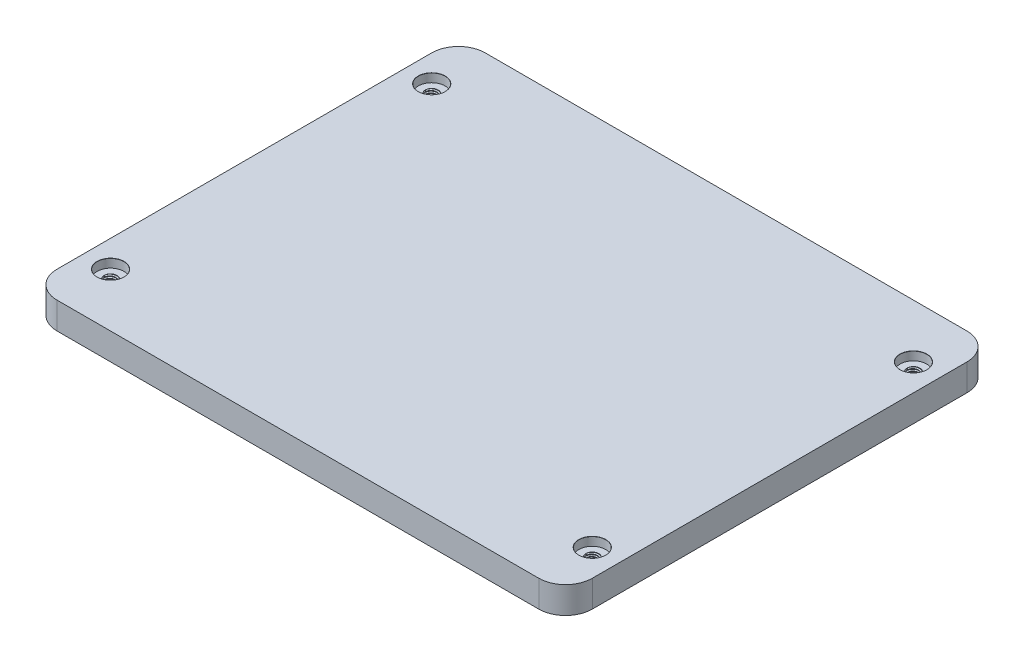
SolidWorks part; units mm, degrees
material "Polylactic Acid (PLA)"
ref_plane "Front Plane" through (0, 0, 0) normal (0, 0, 1) x (1, 0, 0)
ref_plane "Top Plane" through (0, 0, 0) normal (0, 1, 0) x (1, 0, 0)
ref_plane "Right Plane" through (0, 0, 0) normal (1, 0, 0) x (0, 0, -1)
sketch "Sketch1" plane through (0, 0, 0) normal (0, 1, 0) x (1, 0, 0)
  line L1 (-50, 40) -> (50, 40)
  line L2 (-50, 40) -> (-50, -40)
  line L3 (-50, -40) -> (50, -40)
  line L4 (50, 40) -> (50, -40)
extrude "Boss-Extrude1" add sketch "Sketch1" along normal blind 5
fillet "Fillet1" radius 5 4 edges at (-50, 2.5, 40) (-50, 2.5, -40) (50, 2.5, -40) (50, 2.5, 40)
sketch "Sketch4" plane through (0, 0, 0) normal (0, -1, 0) x (1, 0, 0)
  line L0 (50, 35) -> (40, 35) construction
  line L1 (45, 40) -> (45, 30) construction
  line L2 (45, 30) -> (40, 30) construction
  line L3 (24.1369, 29.0334) -> (25.2186, 29.3663)
  line L4 (40, 30) -> (40, 35) construction
  line L7 (20, 22.5) -> (40, 22.5) construction
  line L8 (23.9911, 24.9279) -> (23.9911, 25.2881)
  line L9 (20, 15) -> (20, 30) construction
  line L10 (16.6771, 32.2424) -> (65.1289, 32.2424) construction
  line L11 (23.4179, 28.3033) -> (23.5685, 27.8658)
  line L12 (23.8006, 27.664) -> (23.6379, 27.664)
  line L13 (23.6132, 27.7358) -> (23.6379, 27.664)
  line L14 (25.2186, 24.795) -> (25.2186, 25.166)
  line L15 (25.2186, 24.795) -> (25.6926, 24.5777)
  line L16 (25.6926, 24.5777) -> (25.6926, 24.3305)
  line L17 (25.6926, 24.3305) -> (24.1369, 24.3305)
  line L18 (24.1369, 24.3305) -> (24.1369, 24.5777)
  line L19 (24.1369, 24.5777) -> (24.6778, 24.7441)
  line L20 (24.6778, 24.7441) -> (24.6778, 25.2482)
  line L21 (24.6778, 28.7221) -> (24.1369, 29.0334)
  line L22 (25.7907, 27.4095) -> (25.8287, 27.4185)
  line L23 (26.8715, 27.664) -> (26.8715, 27.3265)
  line L24 (25.7907, 27.2758) -> (25.8287, 27.2595)
  line L25 (25.7907, 27.2758) -> (25.7907, 27.4095)
  line L26 (26.276, 26.9098) -> (26.276, 25.9631)
  line L27 (27.7806, 27.4095) -> (28.1923, 27.504)
  line L28 (28.8891, 27.664) -> (28.8891, 27.4814)
  line L29 (28.8891, 24.9279) -> (29.3631, 24.7441)
  line L30 (29.3631, 24.7441) -> (29.3631, 24.5777)
  line L31 (29.3631, 24.5777) -> (28.3348, 24.3416)
  line L32 (28.3348, 24.3416) -> (28.3348, 24.7679)
  line L33 (27.7806, 27.2758) -> (27.7806, 27.4095)
  line L34 (28.2206, 27.1421) -> (27.7806, 27.2758)
  line L35 (28.3348, 27.0667) -> (28.3348, 27.0272)
  line L36 (28.3348, 27.0667) -> (28.2206, 27.1421)
  line L37 (31.8159, 27.5597) -> (31.8159, 26.8495)
  line L38 (31.6365, 26.6106) -> (31.8159, 26.6106)
  line L39 (29.653, 25.3798) -> (29.653, 25.3136)
  line L40 (29.653, 25.3798) -> (29.8723, 25.3798)
  line L41 (32.7631, 28.4005) -> (33.2555, 28.4866)
  line L42 (33.2555, 28.4866) -> (33.2555, 27.664)
  line L43 (33.2555, 27.664) -> (34.388, 27.664)
  line L44 (23.8006, 28.753) -> (23.8607, 28.7221)
  line L45 (34.388, 27.664) -> (34.3549, 27.5597)
  line L46 (34.2649, 27.2758) -> (33.2555, 27.2758)
  line L47 (33.2555, 27.2758) -> (33.2555, 27.1421)
  line L48 (34.3223, 24.795) -> (34.3223, 24.6583)
  line L49 (32.1722, 27.4814) -> (32.1722, 27.2758)
  line L50 (32.1722, 27.2758) -> (32.6728, 27.2758)
  line L51 (32.6728, 27.2758) -> (32.6728, 26.7919)
  line L52 (35.102, 26.6106) -> (35.102, 26.4555)
  line L53 (35.102, 26.4555) -> (35.7179, 26.4555)
  line L54 (35.102, 26.2142) -> (35.7445, 26.2142)
  line L55 (37.1536, 26.2142) -> (37.1536, 26.3177)
  line L56 (35.9575, 26.2142) -> (36.7435, 26.2142)
  line L57 (35.102, 26.2142) -> (35.102, 25.909)
  line L58 (37.1536, 25.0961) -> (37.1536, 24.795)
  line L59 (38.4913, 26.989) -> (38.4913, 27.664)
  line L60 (38.4913, 27.664) -> (37.4409, 27.4095)
  line L61 (37.4409, 27.4095) -> (37.4409, 27.2758)
  line L62 (37.4409, 27.2758) -> (37.7609, 27.223)
  line L63 (37.7609, 27.223) -> (37.8963, 27.034)
  line L64 (37.8963, 27.034) -> (37.8963, 26.6828)
  line L65 (37.8963, 24.795) -> (37.7609, 24.6596)
  line L66 (37.7609, 24.6596) -> (37.4409, 24.582)
  line L67 (37.4409, 24.582) -> (37.4409, 24.3957)
  line L68 (37.4409, 24.3957) -> (39.0904, 24.3957)
  line L69 (39.0904, 24.3957) -> (39.0904, 24.582)
  line L70 (39.0904, 24.582) -> (38.6208, 24.6596)
  line L71 (38.6208, 24.6596) -> (38.4913, 24.7891)
  line L72 (38.4913, 26.7674) -> (38.4913, 26.5402)
  line L73 (39.9275, 27.5597) -> (39.9275, 26.8166)
  line L74 (39.9275, 26.8166) -> (39.8208, 26.8166)
  line L75 (39.8208, 26.8166) -> (39.7141, 26.8166)
  line L76 (22.0048, 27.2602) -> (21.8423, 26.5307)
  line L77 (21.9179, 26.505) -> (22.1161, 27.2073)
  line L78 (22.103, 26.0379) -> (22.7036, 25.7137)
  line L79 (22.6206, 25.574) -> (22.0162, 25.909)
  line L80 (23.2002, 25.7455) -> (23.3743, 26.3369)
  line L81 (23.052, 25.8181) -> (23.2002, 26.406)
  line L82 (23.181, 26.9798) -> (22.5733, 27.4814)
  line L83 (23.0812, 26.8446) -> (22.4979, 27.3265)
  line L84 (22.2908, 27.2013) -> (22.5114, 26.5687)
  line L85 (22.5733, 26.3912) -> (22.7868, 25.779)
  line L86 (23.0578, 26.7674) -> (22.6689, 26.62)
  line L87 (23.0762, 26.5687) -> (22.737, 26.4402)
  line L88 (22.5114, 26.5687) -> (22.0453, 26.4061)
  line L89 (22.5733, 26.3912) -> (22.1238, 26.2344)
  line L90 (22.5666, 27.664) -> (23.5685, 27.8658)
  line L91 (22.5811, 27.5368) -> (23.6132, 27.7358)
  line L92 (23.865, 25.4242) -> (23.3346, 25.4845)
  line L93 (23.3261, 25.3798) -> (23.865, 25.2881)
  line L94 (23.865, 25.4242) -> (24.6778, 25.3798)
  line L95 (23.9911, 25.2881) -> (24.6778, 25.2482)
  line L96 (25.2186, 25.3259) -> (25.427, 25.2833)
  line L97 (25.2186, 25.166) -> (25.4322, 25.134)
  line L98 (23.7275, 26.505) -> (24.6778, 25.9051)
  line L99 (23.6379, 26.4078) -> (24.6778, 25.7455)
  line L100 (25.2186, 25.574) -> (25.482, 25.4059)
  line L101 (25.2186, 25.4059) -> (25.4319, 25.3041)
  line L102 (23.7779, 26.7674) -> (24.6778, 26.8446)
  line L103 (23.7729, 26.6106) -> (24.6778, 26.7005)
  line L104 (23.6547, 26.9798) -> (24.6778, 27.5942)
  line L105 (23.7545, 26.8446) -> (24.6778, 27.3711)
  line L106 (23.8006, 27.9163) -> (24.6778, 28.0839)
  line L107 (23.8006, 27.7358) -> (24.6778, 27.9478)
  line L108 (25.2186, 28.188) -> (25.429, 28.245)
  line L109 (25.2186, 27.9972) -> (25.4286, 28.1334)
  line L110 (25.2186, 27.8658) -> (25.4604, 28.0298)
  line L111 (25.2186, 27.693) -> (25.5137, 27.9484)
  line L112 (25.8287, 27.8237) -> (25.8287, 27.4185)
  line L113 (25.9648, 27.8658) -> (25.9648, 27.4505)
  line L114 (25.2186, 26.9326) -> (25.8287, 27.01)
  line L115 (25.9648, 27.0272) -> (26.276, 27.0667)
  line L116 (25.8287, 27.2595) -> (25.8287, 27.01)
  line L117 (25.9648, 27.2008) -> (25.9648, 27.0272)
  line L118 (25.8287, 26.8495) -> (25.7907, 25.5752)
  line L119 (25.9648, 26.8679) -> (25.9207, 25.5513)
  line L120 (25.9648, 25.5312) -> (26.276, 25.9631)
  line L121 (26.056, 25.4614) -> (26.276, 25.7137)
  line L122 (26.0994, 25.4059) -> (26.276, 25.4614)
  line L123 (26.1361, 25.3306) -> (26.276, 25.3798)
  line L124 (26.0081, 27.8933) -> (26.3582, 27.5432)
  line L125 (26.0994, 27.991) -> (26.527, 27.5829)
  line L126 (27.0412, 26.7674) -> (26.8715, 26.5687)
  line L127 (26.9114, 26.9326) -> (26.8715, 26.8927)
  line L128 (26.8715, 27.3265) -> (26.9497, 27.2731)
  line L129 (26.8939, 27.1421) -> (26.8715, 27.1421)
  line L130 (27.4632, 26.7674) -> (27.711, 26.2685)
  line L131 (27.3697, 26.7198) -> (27.5783, 26.2142)
  line L132 (27.6163, 27.0272) -> (28.3348, 27.0272)
  line L133 (27.5783, 26.9) -> (28.3348, 26.9)
  line L134 (26.8939, 27.9647) -> (28.4733, 27.5686)
  line L135 (26.121, 28.0298) -> (28.1923, 27.504)
  line L136 (27.4144, 25.909) -> (26.8715, 25.7137)
  line L137 (27.4529, 25.7455) -> (26.8715, 25.5312)
  line L138 (28.143, 25.8562) -> (28.3348, 25.779)
  line L139 (28.0612, 25.6737) -> (28.3348, 25.6171)
  line L140 (28.1233, 26.0379) -> (28.3348, 26.1175)
  line L141 (28.143, 25.8562) -> (28.3348, 25.909)
  line L142 (26.1528, 28.1334) -> (31.9533, 28.0839)
  line L143 (31.8601, 27.9176) -> (26.8939, 27.9647)
  line L144 (28.8891, 27.4814) -> (29.8544, 27.1421)
  line L145 (28.8891, 27.2758) -> (29.7792, 27.0065)
  line L146 (28.8891, 27.0065) -> (29.7792, 27.0065)
  line L147 (28.8891, 26.8495) -> (29.7135, 26.8166)
  line L148 (28.8891, 26.296) -> (29.6945, 26.5298)
  line L149 (28.8891, 26.0923) -> (29.7213, 26.3818)
  line L150 (28.8891, 25.574) -> (29.653, 25.3136)
  line L151 (28.8891, 25.4059) -> (29.653, 25.134)
  line L152 (29.8846, 25.2482) -> (30.3505, 25.0581)
  line L153 (29.9427, 25.0581) -> (30.3234, 24.9197)
  line L154 (30.6896, 25.7137) -> (30.6896, 25.2859)
  line L155 (30.8482, 25.6638) -> (30.8482, 25.2498)
  line L156 (30.8831, 26.3177) -> (30.8831, 26.4109)
  line L157 (30.6896, 26.418) -> (30.6896, 26.3818)
  line L158 (30.9866, 25.134) -> (31.3847, 25.4213)
  line L159 (31.1642, 25.0961) -> (31.4723, 25.2859)
  line L160 (31.1642, 25.0961) -> (31.5169, 25.113)
  line L161 (31.0558, 24.9197) -> (31.4852, 24.9655)
  line L162 (30.5077, 26.989) -> (30.2376, 27.0667)
  line L163 (30.4364, 26.8166) -> (30.2071, 26.8166)
  line L164 (30.4364, 26.8166) -> (30.2138, 26.7674)
  line L165 (30.2758, 26.6106) -> (30.4484, 26.6623)
  line L166 (30.9866, 27.082) -> (31.1904, 27.2859)
  line L167 (31.0908, 26.989) -> (31.3189, 27.217)
  line L168 (31.1561, 26.8495) -> (31.6028, 26.8495)
  line L169 (31.1593, 26.7005) -> (31.6328, 26.7005)
  line L170 (31.5169, 27.6204) -> (31.8601, 27.9176)
  line L171 (31.7321, 27.5774) -> (32.0422, 27.8447)
  line L172 (32.5087, 27.7703) -> (32.5911, 27.6336)
  line L173 (32.6857, 28.0839) -> (32.7745, 28.0298)
  line L174 (31.8159, 26.8495) -> (32.6728, 26.7919)
  line L175 (31.8159, 26.6623) -> (32.6728, 26.6623)
  line L176 (31.9206, 25.7137) -> (32.6728, 26.1494)
  line L177 (31.9632, 25.5312) -> (32.6728, 25.9631)
  line L178 (31.9854, 25.209) -> (32.6728, 25.2498)
  line L179 (31.9693, 25.0206) -> (32.6728, 25.0961)
  line L180 (33.2555, 27.1421) -> (33.5099, 26.8755)
  line L181 (33.2555, 26.9768) -> (33.443, 26.7892)
  line L182 (33.2555, 26.7674) -> (33.4318, 26.7674)
  line L183 (33.2555, 26.6106) -> (33.3965, 26.6106)
  line L184 (33.2555, 26.4555) -> (33.3989, 26.5687)
  line L185 (33.2555, 26.296) -> (33.4515, 26.4176)
  line L186 (33.2555, 25.3136) -> (34.486, 25.4616)
  line L187 (33.2555, 25.134) -> (34.5302, 25.3139)
  line L188 (34.3549, 27.5597) -> (34.9324, 27.3384)
  line L189 (34.2951, 27.3711) -> (34.8203, 27.2046)
  line L190 (34.692, 27.0062) -> (34.0937, 26.7674)
  line L191 (34.5767, 26.7674) -> (34.1289, 26.6106)
  line L192 (34.4439, 26.1215) -> (34.0602, 26.397)
  line L193 (34.4649, 26.2977) -> (34.1134, 26.505)
  line L194 (35.4524, 26.9326) -> (35.2151, 26.9326)
  line L195 (35.5168, 27.188) -> (35.3905, 27.223)
  line L196 (35.7179, 26.4555) -> (35.688, 26.6336)
  line L197 (35.9062, 26.4555) -> (35.8504, 26.6122)
  line L198 (36.4355, 27.0667) -> (36.1709, 27.0667)
  line L199 (36.5053, 26.8726) -> (36.167, 26.8726)
  line L200 (37.1898, 27.034) -> (37.0286, 27.034)
  line L201 (37.1536, 26.3177) -> (37.2762, 26.4403)
  line L202 (35.6384, 25.3798) -> (35.1985, 25.3798)
  line L203 (35.688, 25.5639) -> (35.102, 25.909)
  line L204 (35.1462, 25.5312) -> (35.4524, 25.5312)
  line L205 (35.4524, 25.5312) -> (35.1079, 25.7339)
  line L206 (35.7445, 26.2142) -> (35.8956, 25.7294)
  line L207 (35.9575, 26.2142) -> (36.0337, 25.7449)
  line L208 (36.2114, 25.6821) -> (36.7435, 26.2142)
  line L209 (36.2919, 25.6069) -> (37.0288, 26.2142)
  line L210 (36.3684, 25.4213) -> (37.8963, 25.3259)
  line L211 (36.3586, 25.2859) -> (37.8963, 25.1899)
  line L212 (37.8009, 26.7005) -> (37.8963, 26.6828)
  line L213 (37.7281, 26.5402) -> (37.8963, 26.4801)
  line L214 (37.7281, 26.5402) -> (37.8963, 26.372)
  line L215 (37.6338, 26.4561) -> (37.8963, 26.1175)
  line L216 (38.4913, 25.7294) -> (38.7058, 25.4845)
  line L217 (38.4913, 25.1899) -> (38.5813, 25.1899)
  line L218 (38.4913, 26.5402) -> (38.8967, 26.4561)
  line L219 (38.4913, 26.3818) -> (38.8947, 26.3177)
  line L220 (39.0384, 26.0867) -> (38.923, 25.5744)
  line L221 (39.1957, 26.0204) -> (39.0904, 25.5459)
  line L222 (22.9691, 25.8276) -> (22.737, 26.4402)
  line L223 (22.6689, 26.62) -> (22.4263, 27.2602)
  line L224 (26.276, 25.7137) -> (26.276, 25.4614)
  line L225 (24.6778, 25.3798) -> (24.6778, 25.7455)
  line L226 (24.6778, 25.9051) -> (24.6778, 26.7005)
  line L227 (24.6778, 26.8446) -> (24.6778, 27.3711)
  line L228 (24.6778, 27.5942) -> (24.6778, 27.9478)
  line L229 (24.6778, 28.0839) -> (24.6778, 28.7221)
  line L230 (23.8006, 27.664) -> (23.8006, 27.7358)
  line L231 (23.8006, 27.9163) -> (23.8607, 28.7221)
  line L232 (25.2186, 25.3259) -> (25.2186, 25.4059)
  line L233 (25.2186, 25.574) -> (25.2186, 26.7674)
  line L234 (25.2186, 26.9326) -> (25.2186, 27.693)
  line L235 (25.2186, 27.8658) -> (25.2186, 27.9972)
  line L236 (25.2186, 28.188) -> (25.2186, 29.3663)
  line L237 (25.9648, 27.4505) -> (26.3582, 27.5432)
  line L238 (26.527, 27.5829) -> (26.8715, 27.664)
  line L239 (25.9648, 27.2008) -> (26.276, 27.0667)
  line L240 (26.276, 26.9098) -> (25.9648, 26.8679)
  line L241 (25.8287, 26.8495) -> (25.2186, 26.7674)
  line L242 (26.8715, 27.1421) -> (26.8715, 26.8927)
  line L243 (26.8715, 26.5687) -> (26.8715, 25.7137)
  line L244 (26.8715, 25.5312) -> (26.8715, 25.3798)
  line L245 (28.3348, 26.9) -> (28.3348, 26.1175)
  line L246 (28.3348, 25.779) -> (28.3348, 25.909)
  line L247 (28.3348, 25.6171) -> (28.3348, 25.0961)
  line L248 (28.4733, 27.5686) -> (28.8891, 27.664)
  line L249 (28.8891, 27.2758) -> (28.8891, 27.0065)
  line L250 (28.8891, 26.8495) -> (28.8891, 26.296)
  line L251 (28.8891, 26.0923) -> (28.8891, 25.574)
  line L252 (28.8891, 25.4059) -> (28.8891, 24.9279)
  line L253 (31.7321, 27.5774) -> (31.8159, 27.5597)
  line L254 (30.2138, 26.7674) -> (30.2071, 26.8166)
  line L255 (31.6328, 26.7005) -> (31.6365, 26.6106)
  line L256 (29.653, 25.134) -> (29.653, 24.4596)
  line L257 (31.8159, 26.6623) -> (31.8159, 26.6106)
  line L258 (32.6728, 26.6623) -> (32.6728, 26.1494)
  line L259 (32.6728, 25.9631) -> (32.6728, 25.2498)
  line L260 (32.6728, 25.0961) -> (32.6728, 24.8552)
  line L261 (33.2555, 26.9768) -> (33.2555, 26.7674)
  line L262 (33.2555, 26.7674) -> (33.2567, 26.7609)
  line L263 (33.2555, 26.6106) -> (33.2555, 26.4555)
  line L264 (33.2555, 25.3136) -> (33.2555, 26.296)
  line L265 (33.2555, 25.0152) -> (33.2555, 25.134)
  line L266 (34.2649, 27.2758) -> (34.2951, 27.3711)
  line L267 (35.9062, 26.4555) -> (36.5053, 26.4555)
  line L268 (37.0288, 26.2142) -> (37.1536, 26.2142)
  line L269 (35.102, 26.2142) -> (35.102, 25.909)
  line L270 (37.8963, 26.4801) -> (37.8963, 26.372)
  line L271 (37.8963, 26.1175) -> (37.8963, 25.3259)
  line L272 (37.8963, 25.1899) -> (37.8963, 24.795)
  line L273 (38.4913, 26.3818) -> (38.4913, 25.7294)
  line L274 (38.4913, 25.1899) -> (38.4913, 24.7891)
  arc A0 (22.4263, 27.2602) -> (22.4979, 27.3265) centre (22.2156, 27.5597) ccw
  arc A1 (22.0453, 26.4061) -> (21.9179, 26.505) centre (21.7627, 26.1733) ccw
  arc A2 (23.7545, 26.8446) -> (23.7779, 26.7674) centre (23.4179, 26.7005) cw
  arc A3 (23.3346, 25.4845) -> (23.2002, 25.7455) centre (22.9691, 25.4614) ccw
  arc A4 (25.429, 28.245) -> (26.1524, 28.1309) centre (25.7907, 28.188) cw
  arc A5 (25.9207, 25.5513) -> (25.9648, 25.5312) centre (25.7907, 25.209) cw
  arc A6 (27.5783, 26.9) -> (27.4632, 26.7674) centre (27.2522, 27.0667) cw
  arc A7 (28.0612, 25.6737) -> (27.4529, 25.7455) centre (27.7806, 25.909) cw
  arc A8 (30.3234, 24.9197) -> (30.5173, 24.5966) centre (30.6896, 24.9197) ccw
  arc A9 (31.1593, 26.7005) -> (30.8831, 26.4109) centre (30.7992, 26.7674) cw
  arc A10 (31.9533, 28.0839) -> (32.6857, 28.0839) centre (32.3195, 28.0839) cw
  arc A11 (34.1289, 26.6106) -> (34.1134, 26.505) centre (33.7627, 26.6106) cw
  arc A12 (35.5168, 27.188) -> (36.1709, 27.0667) centre (35.8159, 26.9768) cw
  arc A13 (36.0337, 25.7449) -> (36.2114, 25.6821) centre (36.0046, 25.3798) cw
  arc A14 (37.1898, 27.034) -> (37.8009, 26.7005) centre (37.4409, 26.7674) cw
  arc A15 (38.8967, 26.4561) -> (39.1957, 26.0204) centre (39.2553, 26.3818) cw
  arc A16 (39.0904, 25.5459) -> (38.5813, 25.1899) centre (38.947, 25.209) cw
  arc A17 (23.052, 25.8181) -> (22.9691, 25.8276) centre (22.9691, 25.4614) ccw
  arc A18 (22.7868, 25.779) -> (22.7036, 25.7137) centre (22.9691, 25.4614) ccw
  arc A19 (22.6206, 25.574) -> (23.3261, 25.3798) centre (22.9691, 25.4614) ccw
  arc A20 (22.103, 26.0379) -> (22.1238, 26.2344) centre (21.7627, 26.1733) ccw
  arc A21 (22.0162, 25.909) -> (21.8423, 26.5307) centre (21.7627, 26.1733) cw
  arc A22 (22.1161, 27.2073) -> (22.2908, 27.2013) centre (22.2156, 27.5597) ccw
  arc A23 (22.5733, 27.4814) -> (22.5811, 27.5368) centre (22.2156, 27.5597) ccw
  arc A24 (22.0048, 27.2602) -> (22.5666, 27.664) centre (22.2156, 27.5597) cw
  arc A25 (23.181, 26.9798) -> (23.6547, 26.9798) centre (23.4179, 26.7005) cw
  arc A26 (23.7729, 26.6106) -> (23.7275, 26.505) centre (23.4179, 26.7005) cw
  arc A27 (23.6379, 26.4078) -> (23.3743, 26.3369) centre (23.4179, 26.7005) cw
  arc A28 (23.2002, 26.406) -> (23.0762, 26.5687) centre (23.4179, 26.7005) cw
  arc A29 (23.0578, 26.7674) -> (23.0812, 26.8446) centre (23.4179, 26.7005) cw
  arc A30 (25.4604, 28.0298) -> (25.4286, 28.1334) centre (25.7907, 28.188) cw
  arc A31 (25.5137, 27.9484) -> (25.8287, 27.8237) centre (25.7907, 28.188) ccw
  arc A32 (25.9648, 27.8658) -> (26.0081, 27.8933) centre (25.7907, 28.188) ccw
  arc A33 (26.0994, 27.991) -> (26.121, 28.0298) centre (25.7907, 28.188) ccw
  arc A34 (25.482, 25.4059) -> (25.7907, 25.5752) centre (25.7907, 25.209) cw
  arc A35 (26.056, 25.4614) -> (26.0994, 25.4059) centre (25.7907, 25.209) cw
  arc A36 (25.4319, 25.3041) -> (25.427, 25.2833) centre (25.7907, 25.209) ccw
  arc A37 (26.1361, 25.3306) -> (25.4322, 25.134) centre (25.7907, 25.209) cw
  arc A38 (26.9497, 27.2731) -> (27.6163, 27.0272) centre (27.2522, 27.0667) cw
  arc A39 (27.3697, 26.7198) -> (27.0412, 26.7674) centre (27.2522, 27.0667) cw
  arc A40 (26.9114, 26.9326) -> (26.8939, 27.1421) centre (27.2522, 27.0667) cw
  arc A41 (27.711, 26.2685) -> (28.1233, 26.0379) centre (27.7806, 25.909) cw
  arc A42 (27.4144, 25.909) -> (27.5783, 26.2142) centre (27.7806, 25.909) cw
  arc A43 (30.3505, 25.0581) -> (30.6896, 25.2859) centre (30.6896, 24.9197) cw
  arc A44 (31.0558, 24.9197) -> (30.8449, 24.5881) centre (30.6896, 24.9197) cw
  arc A45 (30.9866, 25.134) -> (30.8482, 25.2498) centre (30.6896, 24.9197) ccw
  arc A46 (31.0908, 26.989) -> (31.1561, 26.8495) centre (30.7992, 26.7674) cw
  arc A47 (30.6896, 26.418) -> (30.4484, 26.6623) centre (30.7992, 26.7674) cw
  arc A48 (30.5077, 26.989) -> (30.9866, 27.082) centre (30.7992, 26.7674) cw
  arc A49 (32.5087, 27.7703) -> (32.0422, 27.8447) centre (32.3195, 28.0839) cw
  arc A50 (33.5099, 26.8755) -> (34.0937, 26.7674) centre (33.7627, 26.6106) cw
  arc A51 (34.0602, 26.397) -> (33.4515, 26.4176) centre (33.7627, 26.6106) cw
  arc A52 (33.3989, 26.5687) -> (33.3965, 26.6106) centre (33.7627, 26.6106) cw
  arc A53 (33.4318, 26.7674) -> (33.443, 26.7892) centre (33.7627, 26.6106) cw
  arc A54 (33.4318, 26.7674) -> (33.443, 26.7892) centre (33.7627, 26.6106) cw
  arc A55 (37.2762, 26.4403) -> (37.6338, 26.4561) centre (37.4409, 26.7674) ccw
  arc A56 (35.688, 26.6336) -> (35.4524, 26.9326) centre (35.8159, 26.9768) cw
  arc A57 (36.167, 26.8726) -> (35.8504, 26.6122) centre (35.8159, 26.9768) cw
  arc A58 (36.2919, 25.6069) -> (36.3684, 25.4213) centre (36.0046, 25.3798) cw
  arc A59 (35.688, 25.5639) -> (35.8956, 25.7294) centre (36.0046, 25.3798) cw
  arc A60 (36.3586, 25.2859) -> (35.6384, 25.3798) centre (36.0046, 25.3798) cw
  arc A61 (38.8947, 26.3177) -> (39.0384, 26.0867) centre (39.2553, 26.3818) ccw
  arc A62 (38.7058, 25.4845) -> (38.923, 25.5744) centre (38.947, 25.209) cw
  spline S0 degree 3 poles (23.8006, 28.753) (23.0243, 29.1404) (21.083, 29.1726) (19.9024, 26.8216) (20.833, 24.0888) (23.249, 24.1492) (23.9911, 24.9279) knots 0 0 0 0 0.267187 0.468549 0.685025 1 1 1 1
  spline S1 degree 3 poles (23.865, 25.2881) (23.397, 24.5703) (21.4323, 24.5286) (20.9261, 26.4818) (20.8327, 27.9751) (22.1359, 28.9103) (22.9885, 28.4743) (23.4179, 28.3033) knots 0 0 0 0 0.311244 0.483795 0.695631 0.819108 1 1 1 1
  spline S2 degree 3 poles (28.3348, 24.7679) (28.1121, 24.4127) (27.4973, 24.2979) (26.3501, 24.3948) (26.3839, 25.1527) (26.276, 25.3798) knots 0 0 0 0 0.389848 0.700971 1 1 1 1
  spline S3 degree 3 poles (26.8715, 25.3798) (26.8653, 24.6336) (27.9992, 24.5457) (28.3348, 25.0961) knots 0 0 0 0 1 1 1 1
  spline S4 degree 3 poles (29.653, 24.4596) (29.9267, 24.3687) (30.4047, 24.1962) (31.0208, 24.3226) (31.5787, 24.4796) (31.9432, 24.7309) (31.9693, 25.0206) knots 0 0 0 0 0.333928 0.549389 0.698568 1 1 1 1
  spline S5 degree 2 poles (32.7631, 28.4005) (32.811, 28.2172) (32.7745, 28.0298) knots 0 0 0 1 1 1
  spline S6 degree 2 poles (34.4649, 26.2977) (34.4989, 26.5371) (34.5767, 26.7674) knots 0 0 0 1 1 1
  spline S7 degree 3 poles (33.2555, 25.0152) (33.5032, 24.6238) (33.9513, 24.8231) (34.3223, 24.795) knots 0 0 0 0 1 1 1 1
  spline S8 degree 3 poles (34.3223, 24.6583) (34.0874, 24.462) (33.4579, 24.1984) (32.7786, 24.5106) (32.6728, 24.8552) knots 0 0 0 0 0.479275 1 1 1 1
  spline S9 degree 2 poles (35.102, 26.6106) (35.1476, 26.7754) (35.2151, 26.9326) knots 0 0 0 1 1 1
  spline S10 degree 2 poles (35.1079, 25.7339) (35.1187, 25.6309) (35.1462, 25.5312) knots 0 0 0 1 1 1
  spline S12 degree 3 poles (38.4913, 26.989) (38.6078, 27.59) (39.4396, 27.9855) (39.9275, 27.5597) knots 0 0 0 0 1 1 1 1
  spline S13 degree 3 poles (38.4913, 26.7674) (38.6465, 27.1632) (39.6735, 27.55) (39.7141, 26.8166) knots 0 0 0 0 1 1 1 1
  spline S14 degree 1 poles (29.8723, 25.3798) (29.8846, 25.2482) knots 0 0 1 1
  spline S15 degree 2 poles (29.9427, 25.0581) (30.1018, 24.7065) (30.5173, 24.5966) knots 0 0 0 1 1 1
  spline S16 degree 2 poles (30.8449, 24.5881) (31.2556, 24.6303) (31.4852, 24.9655) knots 0 0 0 1 1 1
  spline S17 degree 2 poles (31.5169, 25.113) (31.5127, 25.2039) (31.4723, 25.2859) knots 0 0 0 1 1 1
  spline S18 degree 2 poles (31.3847, 25.4213) (31.175, 25.6582) (30.8482, 25.6638) knots 0 0 0 1 1 1
  spline S19 degree 3 poles (30.6896, 25.7137) (30.3063, 25.8181) (29.8193, 25.9407) (29.7213, 26.3818) knots 0 0 0 0 1 1 1 1
  spline S20 degree 2 poles (29.6945, 26.5298) (29.6806, 26.6751) (29.7135, 26.8166) knots 0 0 0 1 1 1
  spline S21 degree 3 poles (29.8544, 27.1421) (30.198, 27.7246) (30.9333, 27.7388) (31.5169, 27.6204) knots 0 0 0 0 1 1 1 1
  spline S22 degree 2 poles (31.9854, 25.209) (31.9866, 25.3709) (31.9632, 25.5312) knots 0 0 0 1 1 1
  spline S23 degree 3 poles (31.9206, 25.7137) (31.7954, 26.1465) (31.2371, 26.1661) (30.8831, 26.3177) knots 0 0 0 0 1 1 1 1
  spline S24 degree 2 poles (30.6896, 26.3818) (30.4447, 26.4295) (30.2758, 26.6106) knots 0 0 0 1 1 1
  spline S25 degree 3 poles (30.2376, 27.0667) (30.3455, 27.4431) (30.9144, 27.4121) (31.1904, 27.2859) knots 0 0 0 0 1 1 1 1
  spline S26 degree 2 poles (31.3189, 27.217) (31.52, 27.0873) (31.6028, 26.8495) knots 0 0 0 1 1 1
  spline S27 degree 2 poles (32.1722, 27.4814) (32.4339, 27.457) (32.5911, 27.6336) knots 0 0 0 1 1 1
  spline S28 degree 2 poles (34.692, 27.0062) (34.7502, 27.1094) (34.8203, 27.2046) knots 0 0 0 1 1 1
  spline S29 degree 3 poles (34.9324, 27.3384) (35.1737, 27.6051) (35.76, 27.6976) (36.5776, 27.6211) (36.9137, 27.2514) (37.0286, 27.034) knots 0 0 0 0 0.435858 0.689114 1 1 1 1
  spline S30 degree 2 poles (34.4439, 26.1215) (34.4062, 25.7843) (34.486, 25.4616) knots 0 0 0 1 1 1
  spline S31 degree 3 poles (34.5302, 25.3139) (34.6714, 24.7493) (35.7941, 23.8534) (36.7622, 24.5927) (37.1536, 24.795) knots 0 0 0 0 0.572485 1 1 1 1
  spline S32 degree 3 poles (35.3905, 27.223) (35.508, 27.3679) (35.952, 27.6414) (36.345, 27.2621) (36.4355, 27.0667) knots 0 0 0 0 0.460627 1 1 1 1
  spline S33 degree 2 poles (36.5053, 26.8726) (36.5053, 26.664) (36.5053, 26.4555) knots 0 0 0 1 1 1
  spline S34 degree 3 poles (35.1985, 25.3798) (35.3086, 25.1216) (35.8925, 24.3944) (36.8062, 24.9183) (37.1536, 25.0961) knots 0 0 0 0 0.391189 1 1 1 1
extrude "Cut-Extrude4" cut sketch "Sketch4" against normal blind 0.5 contours S34 L202 A60 L211 L272 L65 L66 L67 L68 L69 L70 L71 L274 L217 A16 L221 A15 L218 L72 S13 L75 L74 L73 S12 L59 L60 L61 L62 L63 L64 L212 A14 L200 S29 L188 L45 L43 L42 L41 S5 L173 A10 L142 A4 L108 L236 L3 L21 L229 region at (24.7377, 0, 29.0052)
sketch "Sketch8" plane through (0, 5, 0) normal (0, 1, 0) x (1, 0, 0)
  line L0 (-45, 40) -> (-45, 30) construction
  line L1 (-45, -40) -> (-45, -30) construction
  line L2 (45, 40) -> (45, 30) construction
  line L3 (45, -40) -> (45, -30) construction
hole_wizard "CBORE for M2 Pan Head Machine Screw1" positions "Sketch9" profile "Sketch10" counterbore size "M2" standard "ANSI Metric" end condition through all
sketch "Sketch9" plane through (0, 5, 0) normal (0, 1, 0) x (1, 0, 0)
  point P0 (45, 30)
  point P3 (-45, 30)
  point P6 (-45, -30)
  point P9 (45, -30)
sketch "Sketch10" plane through (45, 5, -30) normal (1, 0, 0) x (0, 0, 1)
  line L0 (0, 0) -> (0, 5)
  line L1 (0, 5) -> (1.2, 5)
  line L3 (1.2, 5) -> (1.2, 1.6)
  line L4 (2.5, 1.6) -> (1.2, 1.6)
  line L5 (2.5, 1.6) -> (2.5, 0.025)
  line L6 (2.5, 0.025) -> (2.525, 0)
  line L7 (2.525, 0) -> (0, 0)
  line L8 (-2.5, 0.025) -> (-2.525, 0) construction
  line L11 (0, -6.35) -> (0, 107.95) construction
  dimension "Thru Hole Dia." = 2.4
  dimension "Thru Hole Depth" = 5
  dimension "C'Bore Dia." = 5
  dimension "C'Bore Depth" = 1.6
  dimension "Near C'Sink Dia." = 5.05
  dimension "Near C'Sink Angle" = 90
thread "Thread1" pitch 0.4 method extrude profile "Thread Profile1" start angle 0, offset 0, length 0, pitch 0.4, diameter 2.4
ref_plane "Plane1" through (-46.2, 3.4, -30) normal (0, 0, 1) x (-1, 0, 0)
sketch "Thread Profile1" plane through (-46.2, 3.4, -30) normal (0, 0, 1) x (-1, 0, 0)
  line L0 (0, 0) -> (0, 0.4) construction
  line L11 (0, 0) -> (0, 0.35)
  line L12 (0, 0.35) -> (-0.2165, 0.225)
  line L13 (-0.2165, 0.225) -> (-0.2165, 0.125)
  line L15 (-0.2165, 0.125) -> (0, 0)
  line L17 (-0.2165, 0.175) -> (0, 0.175) construction
  point P2 (0, 0)
  dimension "Pitch" = 0.4
  dimension "Profile_Angle" = 60
  dimension "Profile_Land" = 0.1
  dimension "Profile_Height" = 0.2165
thread "Thread2" pitch 0.4 method extrude profile "Thread Profile2" start angle 0, offset 0, length 0, pitch 0.4, diameter 2.4
ref_plane "Plane2" through (-46.2, 3.4, 30) normal (0, 0, 1) x (-1, 0, 0)
sketch "Thread Profile2" plane through (-46.2, 3.4, 30) normal (0, 0, 1) x (-1, 0, 0)
  line L0 (0, 0) -> (0, 0.4) construction
  line L11 (0, 0) -> (0, 0.35)
  line L12 (0, 0.35) -> (-0.2165, 0.225)
  line L13 (-0.2165, 0.225) -> (-0.2165, 0.125)
  line L15 (-0.2165, 0.125) -> (0, 0)
  line L17 (-0.2165, 0.175) -> (0, 0.175) construction
  point P2 (0, 0)
  dimension "Pitch" = 0.4
  dimension "Profile_Angle" = 60
  dimension "Profile_Land" = 0.1
  dimension "Profile_Height" = 0.2165
thread "Thread3" pitch 0.4 method extrude profile "Thread Profile3" start angle 0, offset 0, length 0, pitch 0.4, diameter 2.4
ref_plane "Plane3" through (43.8, 3.4, 30) normal (0, 0, 1) x (-1, 0, 0)
sketch "Thread Profile3" plane through (43.8, 3.4, 30) normal (0, 0, 1) x (-1, 0, 0)
  line L0 (0, 0) -> (0, 0.4) construction
  line L11 (0, 0) -> (0, 0.35)
  line L12 (0, 0.35) -> (-0.2165, 0.225)
  line L13 (-0.2165, 0.225) -> (-0.2165, 0.125)
  line L15 (-0.2165, 0.125) -> (0, 0)
  line L17 (-0.2165, 0.175) -> (0, 0.175) construction
  point P2 (0, 0)
  dimension "Pitch" = 0.4
  dimension "Profile_Angle" = 60
  dimension "Profile_Land" = 0.1
  dimension "Profile_Height" = 0.2165
thread "Thread4" pitch 0.4 method extrude profile "Thread Profile4" start angle 0, offset 0, length 0, pitch 0.4, diameter 2.4
ref_plane "Plane4" through (43.8, 3.4, -30) normal (0, 0, 1) x (-1, 0, 0)
sketch "Thread Profile4" plane through (43.8, 3.4, -30) normal (0, 0, 1) x (-1, 0, 0)
  line L0 (0, 0) -> (0, 0.4) construction
  line L11 (0, 0) -> (0, 0.35)
  line L12 (0, 0.35) -> (-0.2165, 0.225)
  line L13 (-0.2165, 0.225) -> (-0.2165, 0.125)
  line L15 (-0.2165, 0.125) -> (0, 0)
  line L17 (-0.2165, 0.175) -> (0, 0.175) construction
  point P2 (0, 0)
  dimension "Pitch" = 0.4
  dimension "Profile_Angle" = 60
  dimension "Profile_Land" = 0.1
  dimension "Profile_Height" = 0.2165
